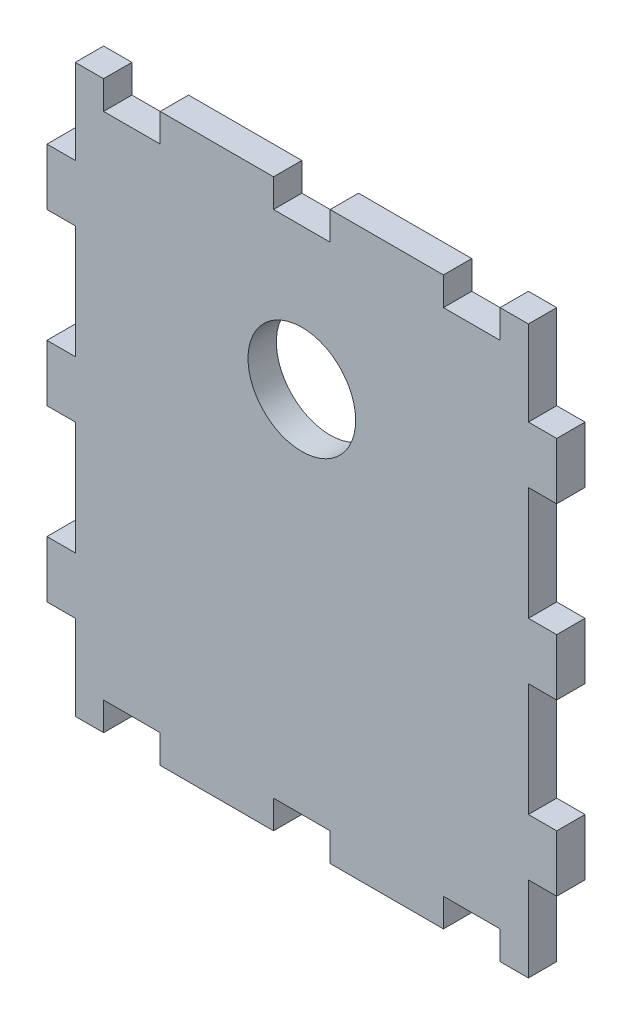
SolidWorks part; units mm, degrees
ref_plane "Ön Düzlem" through (0, 0, 0) normal (0, 0, 1) x (1, 0, 0)
ref_plane "Üst Düzlem" through (0, 0, 0) normal (0, 1, 0) x (1, 0, 0)
ref_plane "Sağ Düzlem" through (0, 0, 0) normal (1, 0, 0) x (0, 0, -1)
sketch "Sketch1" plane through (0, 0, 0) normal (0, 0, 1) x (1, 0, 0)
  line L0 (-35, 50) -> (-35, 45)
  line L1 (-40, -50) -> (-35, -50)
  line L2 (-40, -50) -> (-40, -35)
  line L3 (-40, 50) -> (-35, 50)
  line L4 (40, -50) -> (40, -35)
  line L5 (-40, -50) -> (40, 50) construction
  line L6 (-40, 50) -> (40, -50) construction
  line L7 (-35, 45) -> (-25, 45)
  line L8 (-25, 45) -> (-25, 50)
  line L15 (-5, 45) -> (5, 45)
  line L16 (-5, 50) -> (-5, 45)
  line L17 (5, 45) -> (5, 50)
  line L21 (25, 45) -> (35, 45)
  line L22 (25, 50) -> (25, 45)
  line L23 (35, 45) -> (35, 50)
  line L24 (-40, 35) -> (-45, 35)
  line L25 (-45, 35) -> (-45, 25)
  line L26 (-45, 25) -> (-40, 25)
  line L27 (40, 35) -> (45, 35)
  line L28 (45, 35) -> (45, 25)
  line L29 (45, 25) -> (40, 25)
  line L30 (-45, 5) -> (-45, -5)
  line L31 (-40, 5) -> (-45, 5)
  line L32 (-45, -5) -> (-40, -5)
  line L33 (45, -5) -> (40, -5)
  line L34 (45, 5) -> (45, -5)
  line L35 (40, 5) -> (45, 5)
  line L36 (-45, -25) -> (-45, -35)
  line L37 (-40, -25) -> (-45, -25)
  line L38 (-45, -35) -> (-40, -35)
  line L39 (45, -35) -> (40, -35)
  line L40 (45, -25) -> (45, -35)
  line L41 (40, -25) -> (45, -25)
  line L42 (-25, 50) -> (-5, 50)
  line L43 (5, 50) -> (25, 50)
  line L44 (35, 50) -> (40, 50)
  line L45 (35, -50) -> (40, -50)
  line L46 (5, -50) -> (25, -50)
  line L47 (-25, -50) -> (-5, -50)
  line L48 (-40, -25) -> (-40, -5)
  line L49 (-40, 5) -> (-40, 25)
  line L50 (40, -25) -> (40, -5)
  line L51 (40, 5) -> (40, 25)
  line L52 (40, 35) -> (40, 50)
  line L53 (-40, 35) -> (-40, 50)
  line L54 (-45, -85) -> (-45, -95) [skipped]
  line L55 (-40, -85) -> (-45, -85) [skipped]
  line L56 (-45, -95) -> (-40, -95) [skipped]
  line L57 (45, -95) -> (40, -95) [skipped]
  line L58 (45, -85) -> (45, -95) [skipped]
  line L59 (40, -85) -> (45, -85) [skipped]
  line L60 (45, -65) -> (40, -65) [skipped]
  line L61 (45, -55) -> (45, -65) [skipped]
  line L62 (40, -55) -> (45, -55) [skipped]
  line L63 (-40, -55) -> (-45, -55) [skipped]
  line L64 (-45, -55) -> (-45, -65) [skipped]
  line L65 (-45, -65) -> (-40, -65) [skipped]
  line L66 (-35, -50) -> (-35, -45)
  line L67 (-35, -45) -> (-25, -45)
  line L68 (-25, -45) -> (-25, -50)
  line L69 (5, -45) -> (5, -50)
  line L70 (-5, -45) -> (5, -45)
  line L71 (-5, -50) -> (-5, -45)
  line L72 (35, -45) -> (35, -50)
  line L73 (25, -45) -> (35, -45)
  line L74 (25, -50) -> (25, -45)
  circle A0 centre (0, 20) radius 9.5
  point P0 (0, 0)
  dimension "D18" = 19
  dimension "D1" = 100
  dimension "D2" = 5
  dimension "D3" = 5
  dimension "D4" = 10
  dimension "D6" = 20
  dimension "D7" = 5
  dimension "D8" = 10
  dimension "D9" = 15
  dimension "D11" = 20
  dimension "D12" = 80
  dimension "D13" = 10
  dimension "D14" = 5
  dimension "D15" = 5
  dimension "D17" = 20
  dimension "D19" = 20
  dimension "D5" = 3
  dimension "D10" = 5
  dimension "D16" = 3
extrude "Boss-Extrude1" add sketch "Sketch1" along normal blind 5 contours L27 L52 L44 L23 L21 L22 L43 L17 L15 L16 L42 L8 L7 L0 L3 L49 L31 L30 L32 L48 L37 L36 L38 L2 L1 L67 L47 L46 L45 L4 L39 L40 L41 L50 L33 L34 L35 L51 L29 L28 region at (0, -0.7349, 0)
